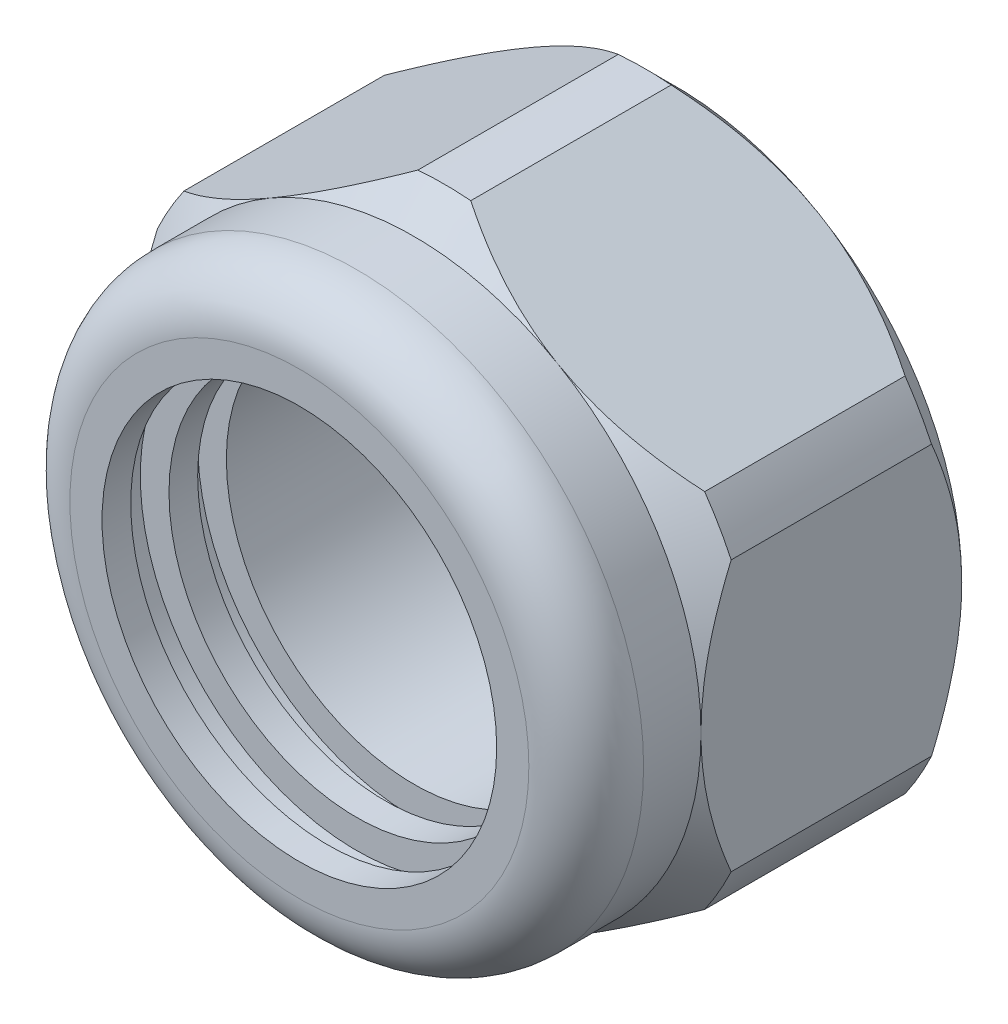
SolidWorks part; units mm, degrees
material "AISI 1020 Сталь, холоднокатаная"
ref_plane "Спереди" through (0, 0, 0) normal (0, 0, 1) x (1, 0, 0)
ref_plane "Сверху" through (0, 0, 0) normal (0, 1, 0) x (1, 0, 0)
ref_plane "Справа" through (0, 0, 0) normal (1, 0, 0) x (0, 0, -1)
sketch "Эскиз2" plane through (0, 0, 0) normal (0, 1, 0) x (1, 0, 0)
  line L0 (0, -84.2304) -> (0, 4127.2879) construction
  line L1 (-18, 25) -> (-18, 0)
  line L2 (-18, 0) -> (-20.75, 0)
  line L3 (-20.75, 0) -> (-20.75, -2.75)
  line L4 (-20.75, -2.75) -> (-18, -2.75)
  line L5 (-18, -2.75) -> (-18, -5.5)
  line L6 (-18, -5.5) -> (-20.75, -5.5)
  line L7 (-20.75, -5.5) -> (-20.75, -8.25)
  line L8 (-20.75, -8.25) -> (-18.9167, -8.25)
  line L9 (-18.9167, -8.25) -> (-18.9167, -11)
  line L10 (-18.9167, -11) -> (-22, -11)
  line L11 (-27.5, -5.5) -> (-27.5, 0)
  line L12 (-27.5, 0) -> (-30.395, 2.895)
  line L13 (-30.395, 2.895) -> (-30.395, 22.105)
  line L14 (-30.395, 22.105) -> (-27.5, 25)
  line L15 (-27.5, 25) -> (-18, 25)
  arc A0 (-27.5, -5.5) -> (-22, -11) centre (-22, -5.5) ccw
  dimension "D4" = 5.5
  dimension "D2" = 2.75
  dimension "D3" = 0.9167
revolve "Повернуть1" add sketch "Эскиз2" angle 360 about L0
sketch "Эскиз3" plane through (0, 0, -25) normal (0, 0, -1) x (-1, 0, 0)
  line L1 (0, -31.7543) -> (27.5, -15.8771)
  line L2 (27.5, -15.8771) -> (27.5, 15.8771)
  line L3 (27.5, 15.8771) -> (0, 31.7543)
  line L4 (0, 31.7543) -> (-27.5, 15.8771)
  line L5 (-27.5, 15.8771) -> (-27.5, -15.8771)
  line L6 (-27.5, -15.8771) -> (0, -31.7543)
  circle A0 centre (0, 0) radius 27.5 construction
  circle A3 centre (0, 0) radius 27.5 construction
extrude "Бобышка-Вытянуть2" add sketch "Эскиз3" against normal up to surface (36 mm away) separate body up to face at (18.9167, 0, 11)
combine bodies "Соединить1" operation type common bodies to combine 104 105
equation "\"D3@Эскиз2\"= \"D2@Эскиз2\" / 3"
equation "\"D4@Эскиз2\"=\"D2@Эскиз2\"*2"
